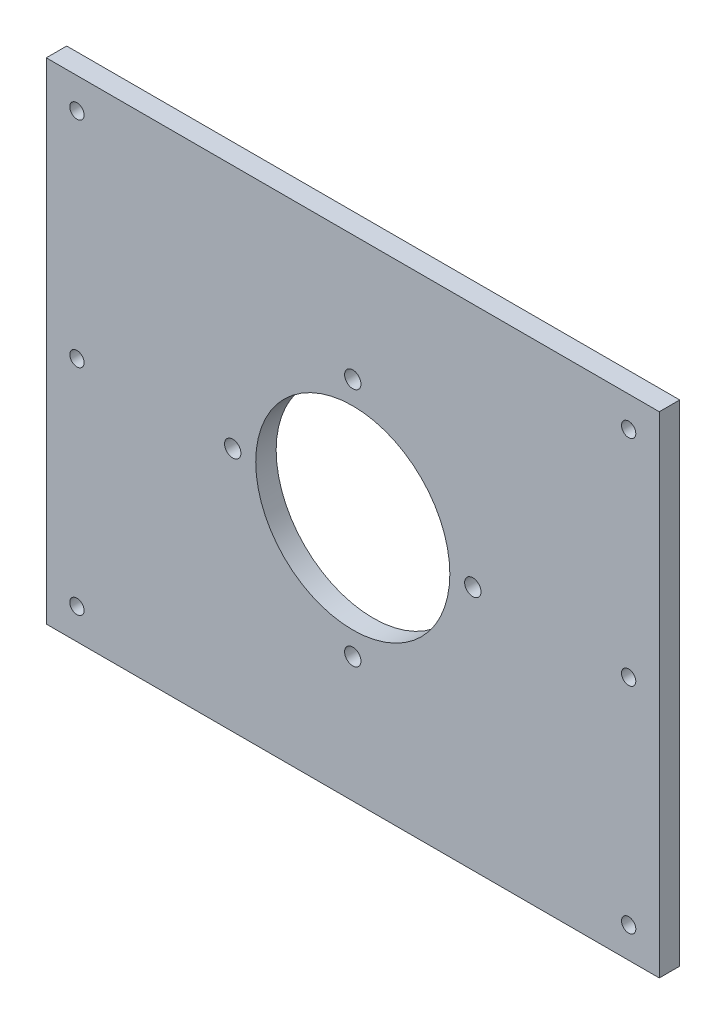
SolidWorks part; units mm, degrees
ref_plane "Front Plane" through (0, 0, 0) normal (0, 0, 1) x (1, 0, 0)
ref_plane "Top Plane" through (0, 0, 0) normal (0, 1, 0) x (1, 0, 0)
ref_plane "Right Plane" through (0, 0, 0) normal (1, 0, 0) x (0, 0, -1)
sketch "Sketch1" plane through (0, 0, 0) normal (0, 0, 1) x (1, 0, 0)
  line L1 (-168.5483, -132.9715) -> (212.4517, -132.9715)
  line L2 (-168.5483, -132.9715) -> (-168.5483, 171.8285)
  line L3 (-168.5483, 171.8285) -> (212.4517, 171.8285)
  line L4 (212.4517, -132.9715) -> (212.4517, 171.8285)
  dimension "D1" = 381
  dimension "D2" = 304.8
extrude "Boss-Extrude1" add sketch "Sketch1" along normal blind 12.7
sketch "Sketch2" plane through (0, 0, 0) normal (0, 0, -1) x (-1, 0, 0)
  line L3 (-212.4517, 171.8285) -> (168.5483, 171.8285) construction
  line L5 (168.5483, 171.8285) -> (168.5483, -132.9715) construction
  line L7 (-21.9517, 19.4285) -> (-96.5517, 19.4285)
  line L8 (-21.9517, 19.4285) -> (-21.9517, -55.1715)
  line L9 (-21.9517, 19.4285) -> (52.6483, 19.4285)
  line L10 (-212.4517, -132.9715) -> (-212.4517, 171.8285) construction
  line L11 (168.5483, -132.9715) -> (-212.4517, -132.9715) construction
  circle A0 centre (-21.9517, 19.4285) radius 74.6
  circle A2 centre (-21.9517, 94.0285) radius 5.08
  circle A3 centre (-96.5517, 19.4285) radius 5.08
  circle A4 centre (52.6483, 19.4285) radius 5.08
  circle A5 centre (-21.9517, -55.1715) radius 5.08
  circle A6 centre (-21.9517, 19.4285) radius 60.325
  circle A7 centre (-193.4017, 152.7785) radius 4.445
  circle A8 centre (-193.4017, -113.9215) radius 4.445
  circle A9 centre (149.4983, -113.9215) radius 4.445
  circle A10 centre (149.4983, 152.7785) radius 4.445
  circle A11 centre (-193.4017, 19.4285) radius 4.445
  circle A12 centre (149.4983, 19.4285) radius 4.445
  point P30 (0, 0)
  point P31 (0, 0)
  dimension "D1" = 149.2
  dimension "D4" = 10.16
  dimension "D5" = 10.16
  dimension "D6" = 10.16
  dimension "D7" = 10.16
  dimension "D8" = 120.65
  dimension "D9" = 8.89
  dimension "D12" = 8.89
  dimension "D15" = 8.89
  dimension "D18" = 8.89
  dimension "D21" = 8.89
  dimension "D24" = 8.89
  dimension "D2" = 152.4
  dimension "D3" = 190.5
  dimension "D10" = 19.05
  dimension "D11" = 19.05
  dimension "D13" = 19.05
  dimension "D14" = 19.05
  dimension "D16" = 19.05
  dimension "D17" = 19.05
  dimension "D19" = 19.05
  dimension "D20" = 19.05
  dimension "D22" = 19.05
  dimension "D23" = 152.4
  dimension "D25" = 19.05
  dimension "D26" = 152.4
extrude "Cut-Extrude1" cut sketch "Sketch2" along normal blind 94.996 and the other way blind 157.226 contours A0 A2 | A0 A2 | L9 A6 L7 | L8 A6 L9 | L7 A6 L8 | A0 A4 | L9 A4 A0 | A0 A5 L8 | L8 A5 A0 | A0 A5 | A0 A3 | L7 A3 A0 | A0 A3 L7 | A12 | A9 | A7 | A8 | A4 | A10 | A11 region at (94.3648, 17.2967, 0) region at (94.3648, 21.5602, 0) region at (98.6762, 19.4285, 0) region at (21.9517, 45.0312, 0) region at (47.5544, -6.1742, 0) region at (-3.6511, -6.1742, 0) region at (21.9517, 96.153, 0) region at (21.9517, 91.8416, 0) region at (24.0834, -52.9846, 0) region at (21.9517, -57.2961, 0) region at (-50.4615, 17.2967, 0) region at (19.8199, -52.9846, 0) region at (-54.7729, 19.4285, 0) region at (193.4017, 152.7785, 0) region at (193.4017, -113.9215, 0) region at (-149.4983, -113.9215, 0) region at (-149.4983, 19.4285, 0)
